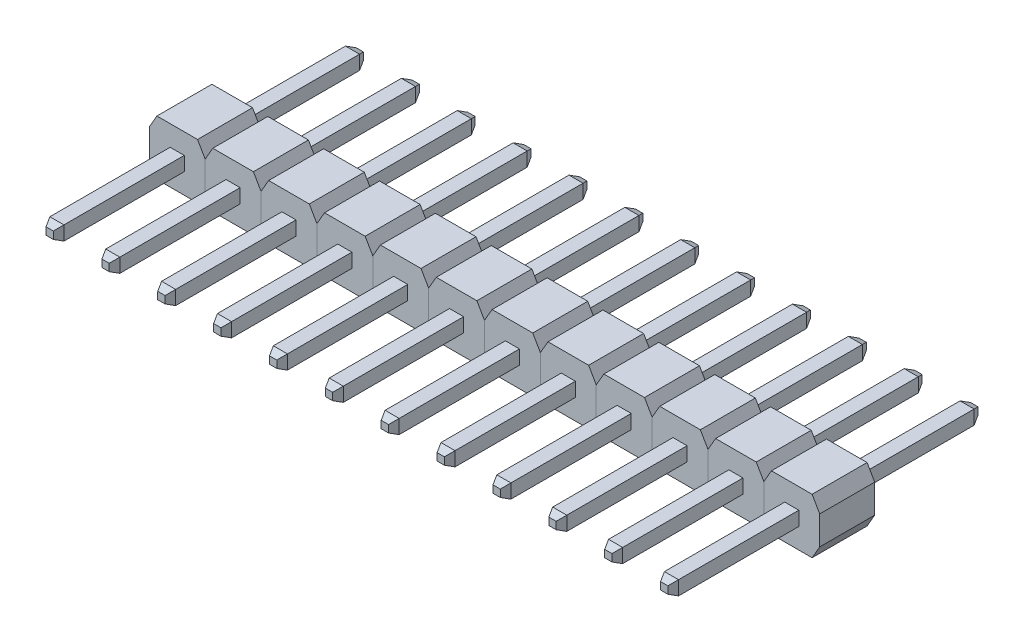
SolidWorks part; units mm, degrees
ref_plane "Спереди" through (0, 0, 0) normal (0, 0, 1) x (1, 0, 0)
ref_plane "Сверху" through (0, 0, 0) normal (0, 1, 0) x (1, 0, 0)
ref_plane "Справа" through (0, 0, 0) normal (1, 0, 0) x (0, 0, -1)
sketch "Эскиз1" plane through (0, 0, 0) normal (0, 0, 1) x (1, 0, 0)
  line L1 (0, 0) -> (0.64, 0)
  line L2 (0, 0) -> (0, -0.64)
  line L3 (0, -0.64) -> (0.64, -0.64)
  line L4 (0.64, 0) -> (0.64, -0.64)
  line L9 (0, -0.64) -> (0.64, 0) construction
  line L14 (1.2436, -1.57) -> (-0.6036, -1.57)
  line L15 (1.59, -0.97) -> (1.59, 0.33)
  line L16 (1.2436, 0.93) -> (-0.6036, 0.93)
  line L17 (-0.95, -0.97) -> (-0.95, 0.33)
  line L18 (1.59, -1.57) -> (-0.95, 0.93) construction
  line L19 (1.59, 0.93) -> (-0.95, -1.57) construction
  line L47 (1.59, 0.33) -> (1.2436, 0.93)
  line L56 (-0.95, 0.33) -> (-0.6036, 0.93)
  line L57 (-0.6036, -1.57) -> (-0.95, -0.97)
  line L58 (1.2436, -1.57) -> (1.59, -0.97)
  point P11 (0.32, -0.32)
  point P15 (0.32, -0.32)
  dimension "D1" = 0.64
  dimension "D2" = 0.64
  dimension "D4" = 30
  dimension "D5" = 0.6
  dimension "D6" = 30
  dimension "D7" = 2.5
  dimension "D8" = 0.6
  dimension "D3" = 0.6
  dimension "D9" = 30
  dimension "D10" = 0.6
  dimension "D11" = 30
extrude "Бобышка-Вытянуть1" add sketch "Эскиз1" along normal blind 2.5 contours L2 L1 L4 L3 | L15 L47 L16 L56 L17 L57 L14 L58
extrude "Бобышка-Вытянуть3" add sketch "Эскиз1<5>" along normal blind 8.3 and the other way blind 5.8 contours L4 L3 L2 L1
sketch "Эскиз1<5>" plane through (0, 0, 0) normal (0, 0, 1) x (1, 0, 0) same geometry as "Эскиз1"
chamfer "Фаска1" distance 0.33 angle 25 4 edges at (0, -0.32, -5.8) (0.32, -0.64, -5.8) (0.64, -0.32, -5.8) (0.32, 0, -5.8) first distance on face at (0, -0.32, -2.9) first distance on face at (0.32, -0.64, -2.9) first distance on face at (0.64, -0.32, -2.9) first distance on face at (0.32, 0, -2.9)
chamfer "Фаска2" distance 0.33 angle 25 4 edges at (0.64, -0.32, 8.3) (0.32, -0.64, 8.3) (0, -0.32, 8.3) (0.32, 0, 8.3) first distance on face at (0.64, -0.32, 5.4) first distance on face at (0.32, -0.64, 5.4) first distance on face at (0, -0.32, 5.4) first distance on face at (0.32, 0, 5.4)
pattern_linear "Линейный массив4" count 12 spacing 2.54 along (-1, 0, 0) of bodies 103
